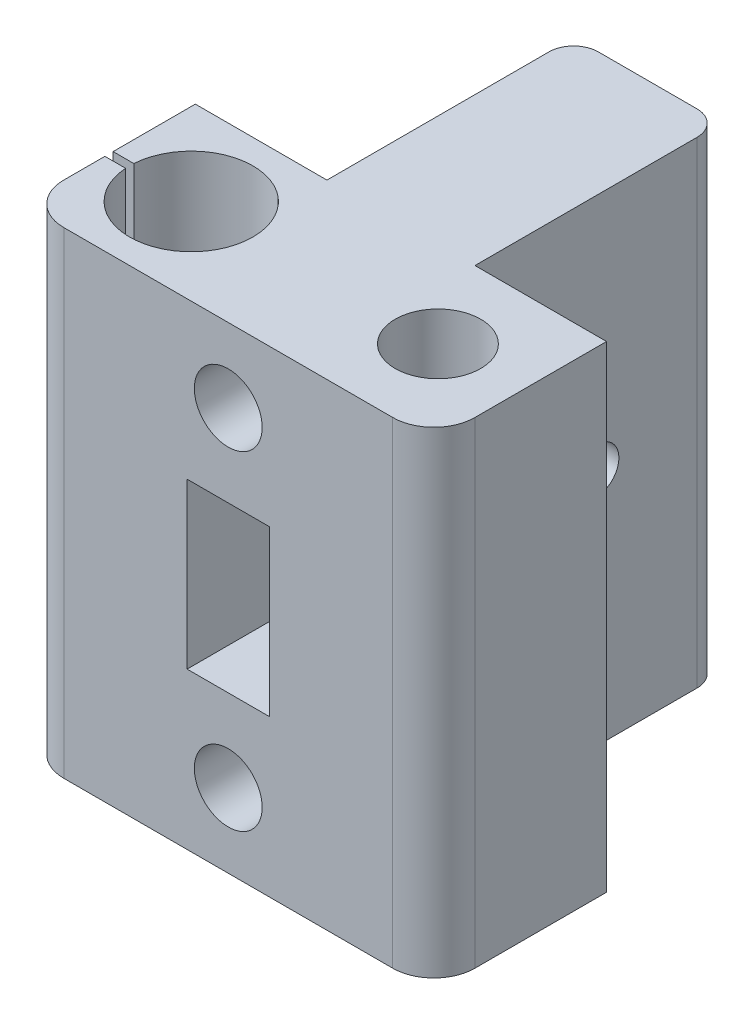
SolidWorks part; units mm, degrees
ref_plane "Front Plane" through (0, 0, 0) normal (0, 0, 1) x (1, 0, 0)
ref_plane "Top Plane" through (0, 0, 0) normal (0, 1, 0) x (1, 0, 0)
ref_plane "Right Plane" through (0, 0, 0) normal (1, 0, 0) x (0, 0, -1)
sketch "Sketch1" plane through (0, 0, 0) normal (0, 1, 0) x (1, 0, 0)
  line L1 (-25, 10.5) -> (25, 10.5)
  line L2 (-25, 10.5) -> (-25, -10.5)
  line L3 (-25, -10.5) -> (25, -10.5)
  line L4 (25, 10.5) -> (25, -10.5)
  line L5 (-25, 10.5) -> (25, -10.5) construction
  line L6 (-25, -10.5) -> (25, 10.5) construction
  point P0 (0, 0)
  dimension "D1" = 21
  dimension "D2" = 50
extrude "Boss-Extrude1" add sketch "Sketch1" along normal blind 58
sketch "Sketch3" plane through (0, 58, 0) normal (0, 1, 0) x (1, 0, 0)
  line L0 (-15, 0) -> (15, 0) construction
  circle A0 centre (-15, 0) radius 7.5
  dimension "D1" = 15
  dimension "D2" = 30
extrude "Cut-Extrude1" cut sketch "Sketch3" against normal blind 24 contours A0
sketch "Sketch4" plane through (0, 58, 0) normal (0, 1, 0) x (1, 0, 0)
  line L0 (-15, 0) -> (15, 0) construction
  circle A0 centre (15, 0) radius 5.2
  dimension "D1" = 10.4
extrude "Cut-Extrude2" cut sketch "Sketch4" against normal up to next
sketch "Sketch5" plane through (0, 0, 0) normal (0, -1, 0) x (1, 0, 0)
  circle A1 centre (-15, 0) radius 7.5
  circle A2 centre (-15, 0) radius 7.5
  dimension "D1" = 0
extrude "Cut-Extrude3" cut sketch "Sketch5" against normal blind 24
sketch "Sketch6" plane through (0, 0, 0) normal (0, -1, 0) x (1, 0, 0)
  circle A0 centre (-15, 0) radius 4.5
extrude "Cut-Extrude4" cut sketch "Sketch6" against normal up to next
sketch "Sketch8" plane through (0, 0, 10.5) normal (0, 0, 1) x (1, 0, 0)
  line L0 (-25, 29) -> (25, 29) construction
  line L1 (-25, 58) -> (-25, 0) construction
  line L2 (25, 58) -> (25, 0) construction
  line L3 (0, 58) -> (0, 0) construction
  line L4 (-25, 58) -> (25, 58) construction
  line L6 (-5, 19) -> (5, 19)
  line L7 (-5, 19) -> (-5, 39)
  line L8 (-5, 39) -> (5, 39)
  line L9 (5, 19) -> (5, 39)
  line L10 (-5, 19) -> (5, 39) construction
  line L11 (-5, 39) -> (5, 19) construction
  point P11 (0, 29)
  dimension "D1" = 20
  dimension "D2" = 10
extrude "Cut-Extrude5" cut sketch "Sketch8" against normal up to next
sketch "Sketch10" plane through (0, 0, -10.5) normal (0, 0, -1) x (-1, 0, 0)
  line L0 (-25, 29) -> (25, 29) construction
  line L1 (-25, 58) -> (-25, 0) construction
  line L2 (25, 58) -> (25, 0) construction
  line L3 (0, 58) -> (0, 0) construction
  line L4 (-25, 58) -> (25, 58) construction
sketch "Sketch11" plane through (0, 0, -10.5) normal (0, 0, -1) x (-1, 0, 0)
  line L0 (-25, 29) -> (25, 29) construction
  line L1 (9, 39) -> (5, 39)
  line L2 (9, 39) -> (9, 19)
  line L3 (9, 19) -> (5, 19)
  line L4 (5, 39) -> (5, 19)
  line L5 (9, 39) -> (5, 19) construction
  line L6 (9, 19) -> (5, 39) construction
  line L7 (0, 58) -> (0, 0) construction
  line L8 (0, 58) -> (0, 0)
  line L9 (-9, 19) -> (-5, 19)
  line L10 (-5, 39) -> (-5, 19)
  line L11 (-9, 39) -> (-5, 39)
  line L12 (-9, 39) -> (-9, 19)
  point P0 (7, 29)
  line M7 (-5, 19) -> (-5, 39)
  line M9 (5, 39) -> (5, 19)
  dimension "D1" = 5
  dimension "D2" = 4
  dimension "D3" = 20
extrude "Boss-Extrude2" add sketch "Sketch11" along normal blind 26 contours L1 L4 L3 L2 M9 | L11 L12 L9 L10 M7 region at (-7, 29, -10.5) region at (7, 29, -10.5)
sketch "Sketch12" plane through (0, 0, -36.5) normal (0, 0, -1) x (-1, 0, 0)
  line L1 (9, 19) -> (-9, 19)
  line L2 (9, 19) -> (9, 39)
  line L3 (9, 39) -> (-9, 39)
  line L4 (-9, 19) -> (-9, 39)
extrude "Boss-Extrude3" add sketch "Sketch12" along normal blind 4
sketch "Sketch13" plane through (9, 0, 0) normal (1, 0, 0) x (0, 0, -1)
  line L3 (10.5, 29) -> (40.5, 29) construction
  line L4 (10.5, 39) -> (10.5, 19) construction
  line L5 (40.5, 39) -> (40.5, 19) construction
  line L6 (16.25, 29) -> (25.25, 29) construction
  line L7 (16.25, 31.75) -> (25.25, 31.75)
  line L8 (16.25, 26.25) -> (25.25, 26.25)
  arc A0 (16.25, 31.75) -> (16.25, 26.25) centre (16.25, 29) ccw
  arc A1 (25.25, 26.25) -> (25.25, 31.75) centre (25.25, 29) ccw
  point P1 (13.5, 29)
  point P14 (20.75, 29)
  dimension "D1" = 5.5
  dimension "D2" = 3
  dimension "D3" = 9
extrude "Cut-Extrude7" cut sketch "Sketch13" against normal through all
fillet "Fillet1" radius 5 2 edges at (-25, 29, 10.5) (25, 29, 10.5)
sketch "Sketch14" plane through (0, 0, 0) normal (0, -1, 0) x (1, 0, 0)
  line L0 (20.5508, 5.5508) -> (9.4492, -5.5508) construction
  line L1 (25, -10.5) -> (-25, -10.5) construction
  circle A0 centre (20.5508, 5.5508) radius 1.95
  circle A1 centre (15, 0) radius 5.2 construction
  circle A2 centre (9.4492, -5.5508) radius 1.95
  circle A3 centre (15, 0) radius 5.2 construction
  dimension "D1" = 7.85
  dimension "D2" = 3.9
  dimension "D3" = 3.9
  dimension "D4" = 7.85
  dimension "D5" = 45
extrude "Cut-Extrude8" cut sketch "Sketch14" against normal blind 10
sketch "Sketch15" plane through (0, 58, 0) normal (0, 1, 0) x (1, 0, 0)
  line L0 (-25, 10.5) -> (-25, -5.5) construction
  line L1 (-25, -0.5) -> (-19.4721, -0.5)
  line L2 (-25, -0.5) -> (-25, 0.5)
  line L3 (-25, 0.5) -> (-19.4721, 0.5)
  line L4 (-19.4721, -0.5) -> (-19.4721, 0.5)
  circle A2 centre (-15, 0) radius 4.5 construction
  dimension "D1" = 1
extrude "Cut-Extrude9" cut sketch "Sketch15" against normal through all
sketch "Sketch17" plane through (9, 0, 0) normal (1, 0, 0) x (0, 0, -1)
  line L0 (10.5, 39) -> (10.5, 58)
  line L1 (10.5, 58) -> (40.5, 58)
  line L2 (40.5, 58) -> (40.5, 39)
  line L3 (40.5, 39) -> (10.5, 39)
  line L4 (10.5, 19) -> (10.5, 0)
  line L5 (10.5, 0) -> (40.5, 0)
  line L6 (40.5, 0) -> (40.5, 19)
  line L7 (40.5, 19) -> (10.5, 19)
  point P10 (0, 0)
extrude "Boss-Extrude5" add sketch "Sketch17" against normal up to surface (18 mm away) up to face at (-9, 29, -20.75)
sketch "Sketch7" plane through (0, 0, 10.5) normal (0, 0, 1) x (1, 0, 0)
  line L0 (0, 58) -> (0, 0) construction
  line L1 (-20, 58) -> (20, 58) construction
  line L2 (-20, 0) -> (20, 0) construction
  line L3 (-25, 29) -> (25, 29) construction
  line L4 (-25, 58) -> (-25, 0) construction
  line L5 (25, 58) -> (25, 0) construction
  circle A1 centre (0, 49) radius 4.125
  circle A2 centre (0, 9) radius 4.125
  point P24 (0, 9)
  dimension "D1" = 8.25
  dimension "D2" = 9
extrude "Cut-Extrude6" cut sketch "Sketch7" against normal blind 45
fillet "Fillet8" radius 3 2 edges at (-9, 29, -40.5) (9, 29, -40.5)
sketch "Sketch18" plane through (0, 0, -40.5) normal (0, 0, -1) x (-1, 0, 0)
  line L0 (-3, 26.25) -> (3, 26.25)
  line L1 (3, 26.25) -> (3, 31.75)
  line L2 (3, 31.75) -> (-3, 31.75)
  line L3 (-3, 31.75) -> (-3, 26.25)
  line L4 (-5, 26.25) -> (-9, 26.25) construction
  line L6 (6, 0) -> (6, 58) construction
  point P6 (0, 0)
  dimension "D1" = 5.5
  dimension "D2" = 6
  dimension "D3" = 3
extrude "Cut-Extrude10" cut sketch "Sketch18" against normal blind 1 contours L2 L3 L0 L1
